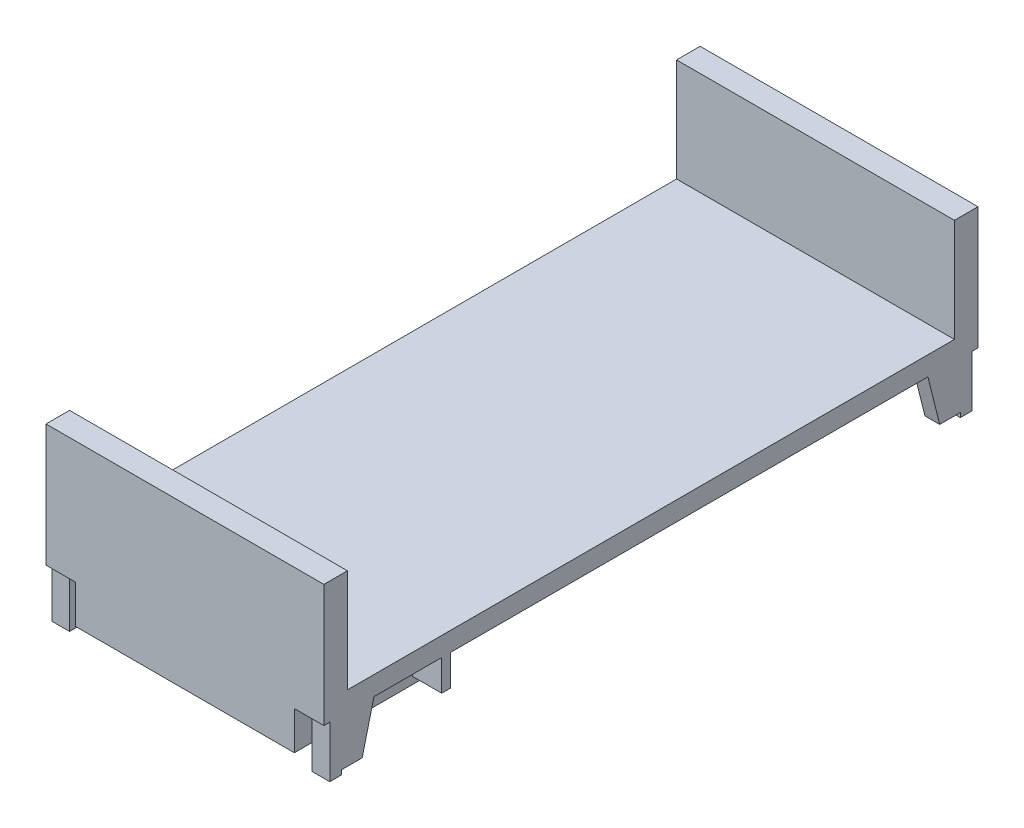
SolidWorks part; units mm, degrees
note: The reader was unsure of these and kept them because the rebuilt part matched: shared geometry of "Sketch1<3>", "Sketch1<4>", "Sketch9<3>".
ref_plane "Front Plane" through (0, 0, 0) normal (0, 0, 1) x (1, 0, 0)
ref_plane "Top Plane" through (0, 0, 0) normal (0, 1, 0) x (1, 0, 0)
ref_plane "Right Plane" through (0, 0, 0) normal (1, 0, 0) x (0, 0, -1)
sketch "Sketch1" plane through (0, 0, 0) normal (0, 1, 0) x (1, 0, 0)
  line L0 (-411.5, 40) -> (-451.5, 40)
  line L1 (451.5, 0) -> (-451.5, 0)
  line L2 (451.5, 0) -> (451.5, 2180)
  line L3 (451.5, 2180) -> (-451.5, 2180)
  line L4 (-451.5, 0) -> (-451.5, 2180)
  line L5 (-451.5, 0) -> (451.5, 0)
  line L6 (-451.5, 0) -> (-451.5, 50)
  line L7 (-451.5, 50) -> (451.5, 50)
  line L8 (451.5, 0) -> (451.5, 50)
  line L9 (-451.5, 2180) -> (451.5, 2180)
  line L10 (-451.5, 2180) -> (-451.5, 2130)
  line L11 (-451.5, 2130) -> (451.5, 2130)
  line L12 (451.5, 2180) -> (451.5, 2130)
  line L13 (451.5, 0) -> (411.5, 0)
  line L14 (451.5, 0) -> (451.5, 50)
  line L15 (451.5, 50) -> (411.5, 50)
  line L16 (411.5, 0) -> (411.5, 50)
  line L17 (-451.5, 0) -> (-411.5, 0)
  line L18 (-451.5, 0) -> (-451.5, 50)
  line L19 (-451.5, 50) -> (-411.5, 50)
  line L20 (-411.5, 0) -> (-411.5, 50)
  line L21 (-451.5, 2130) -> (-411.5, 2130)
  line L22 (-451.5, 2130) -> (-451.5, 2180)
  line L23 (-451.5, 2180) -> (-411.5, 2180)
  line L24 (-411.5, 2130) -> (-411.5, 2180)
  line L25 (451.5, 2180) -> (411.5, 2180)
  line L26 (451.5, 2180) -> (451.5, 2130)
  line L27 (451.5, 2130) -> (411.5, 2130)
  line L28 (411.5, 2180) -> (411.5, 2130)
  line L29 (451.5, 40) -> (411.5, 40)
  line L30 (-451.5, 2140) -> (-411.5, 2140)
  line L31 (411.5, 2140) -> (451.5, 2140)
  line L33 (-471.5, 2200) -> (471.5, 2200)
  line L34 (-471.5, 2200) -> (-471.5, 2120)
  line L35 (-471.5, 2120) -> (471.5, 2120)
  line L36 (471.5, 2200) -> (471.5, 2120)
  line L37 (-471.5, 60) -> (471.5, 60)
  line L38 (-471.5, 60) -> (-471.5, -20)
  line L39 (-471.5, -20) -> (471.5, -20)
  line L40 (471.5, 60) -> (471.5, -20)
  dimension "D1" = 2180
  dimension "D2" = 903
  dimension "D3" = 50
  dimension "D4" = 50
  dimension "D5" = 40
  dimension "D6" = 40
  dimension "D7" = 40
  dimension "D8" = 40
  dimension "D9" = 40
  dimension "D10" = 40
  dimension "D11" = 40
  dimension "D12" = 20
  dimension "D13" = 10
  dimension "D14" = 20
  dimension "D15" = 20
  dimension "D16" = 10
  dimension "D17" = 20
  dimension "D18" = 20
  dimension "D19" = 20
extrude "Boss-Extrude1" add sketch "Sketch1" against normal blind 65 contours L4 L37 L2 L35
extrude "Boss-Extrude2" add sketch "Sketch1<3>" against normal blind 50 and the other way blind 350 contours L38 L39 L40 L37 | L33 L36 L35 L34
sketch "Sketch1<3>" plane through (0, 0, 0) normal (0, 1, 0) x (1, 0, 0) same geometry as "Sketch1"
extrude "Boss-Extrude3" add sketch "Sketch1<4>" against normal blind 240 contours L28 L31 L26 L3 | L22 L30 L24 L9 | L1 L20 L0 L4 | L2 L29 L16 L1
sketch "Sketch1<4>" plane through (0, 0, 0) normal (0, 1, 0) x (1, 0, 0) same geometry as "Sketch1"
sketch "Sketch3" plane through (451.5, 0, 0) normal (1, 0, 0) x (0, 0, -1)
  line L0 (60, -65) -> (2120, -65) construction
  line L3 (40, -225) -> (110, -225)
  line L4 (2140, -240) -> (2140, -65) construction
  line L5 (2030, -65) -> (2070, -225)
  line L6 (2070, -225) -> (2140, -225)
  line L7 (110, -225) -> (150, -65)
  line L8 (2140, -240) -> (2140, -65) construction
  line L9 (40, -240) -> (40, -65) construction
  line L10 (40, -225) -> (40, -65)
  line L11 (40, -65) -> (150, -65)
  line L12 (2140, -225) -> (2140, -65)
  line L13 (2140, -65) -> (2030, -65)
  dimension "D1" = 160
  dimension "D2" = 110
  dimension "D3" = 160
  dimension "D4" = 110
  dimension "D5" = 70
  dimension "D6" = 70
extrude "Boss-Extrude4" add sketch "Sketch3" against normal blind 30
sketch "Sketch4" plane through (-451.5, 0, -45.75) normal (1, 0, 0) x (0, 0, -1)
  line L0 (2094.25, -225) -> (2094.25, -65)
  line L2 (2094.25, -240) -> (2094.25, -65) construction
  line L3 (104.25, -65) -> (64.25, -225)
  line L5 (1984.25, -65) -> (2024.25, -225)
  line L6 (2024.25, -225) -> (2094.25, -225)
  line L7 (64.25, -225) -> (-5.75, -225)
  line L8 (2094.25, -65) -> (1984.25, -65)
  line L9 (-5.75, -225) -> (-5.75, -65)
  line L10 (-5.75, -65) -> (104.25, -65)
  line L11 (14.25, -65) -> (2074.25, -65) construction
  line L12 (-5.75, -240) -> (-5.75, -65) construction
  dimension "D1" = 110
  dimension "D2" = 160
  dimension "D3" = 110
  dimension "D4" = 160
  dimension "D5" = 70
  dimension "D6" = 70
extrude "Boss-Extrude5" add sketch "Sketch4" along normal blind 30
sketch "Sketch5" plane through (0, -240, 0) normal (0, -1, 0) x (1, 0, 0)
  line L0 (-431.5, -2180) -> (-431.5, 0)
  line L1 (-416.5, -2175) -> (-446.5, -2175)
  line L2 (-416.5, -2175) -> (-416.5, -2145)
  line L3 (-416.5, -2145) -> (-446.5, -2145)
  line L4 (-446.5, -2175) -> (-446.5, -2145)
  line L5 (416.5, -2175) -> (446.5, -2175)
  line L6 (416.5, -2175) -> (416.5, -2145)
  line L7 (416.5, -2145) -> (446.5, -2145)
  line L8 (446.5, -2175) -> (446.5, -2145)
  line L9 (416.5, -35) -> (446.5, -35)
  line L10 (416.5, -35) -> (416.5, -5)
  line L11 (416.5, -5) -> (446.5, -5)
  line L12 (446.5, -35) -> (446.5, -5)
  line L13 (-446.5, -35) -> (-416.5, -35)
  line L14 (-446.5, -35) -> (-446.5, -5)
  line L15 (-446.5, -5) -> (-416.5, -5)
  line L16 (-416.5, -35) -> (-416.5, -5)
  line L17 (-451.5, -2160) -> (451.5, -2160)
  line L18 (-411.5, 0) -> (-451.5, 0) construction
  line L19 (-451.5, 0) -> (-451.5, -40) construction
  line L20 (451.5, 0) -> (411.5, 0) construction
  line L21 (451.5, 0) -> (451.5, -40) construction
  line L22 (-451.5, -20) -> (451.5, -20)
  line L25 (431.5, 0) -> (431.5, -2180)
  line L27 (451.5, -2180) -> (411.5, -2180) construction
  line L32 (451.5, -2140) -> (451.5, -2180) construction
  line L33 (-451.5, -2140) -> (-451.5, -2180) construction
  line L34 (-411.5, -2180) -> (-451.5, -2180) construction
  point P16 (-446.5, -2160)
  point P29 (-431.5, -5)
  point P36 (-446.5, -20)
  point P43 (431.5, -2175)
  dimension "D1" = 30
extrude "Cut-Extrude1" cut sketch "Sketch5" against normal blind 200 contours L4 L3 L2 L1 | L6 L7 L8 L5 | L10 L11 L12 L9 | L14 L15 L16 L13
sketch "Sketch6" plane through (0, 0, 20) normal (0, 0, 1) x (1, 0, 0)
  line L1 (130, -65) -> (-130, -65)
  line L2 (-471.5, -65) -> (471.5, -65) construction
  arc A0 (-130, -65) -> (130, -65) centre (0, -65) ccw
  dimension "D1" = 130
extrude "Boss-Extrude6" add sketch "Sketch6" against normal blind 30
sketch "Sketch7" plane through (0, 0, -2200) normal (0, 0, -1) x (-1, 0, 0)
  line L1 (130, -65) -> (-130, -65)
  line L2 (471.5, -65) -> (-471.5, -65) construction
  arc A0 (130, -65) -> (-130, -65) centre (0, -65) cw
  dimension "D1" = 130
extrude "Boss-Extrude7" add sketch "Sketch7" against normal blind 30
sketch3d "3DSketch1"
  line L0 (0, -195, -10) -> (0, -155, -10)
  line L1 (0, -155, -10) -> (0, -155, -2170)
  line L2 (0, -155, -2170) -> (0, -195, -2170)
  line L3 (0, -195, -2170) -> (0, -195, -10)
  arc A0 (-130, -65, -10) -> (130, -65, -10) centre (0, -65, -10) ccw construction
  arc A1 (130, -65, -2170) -> (-130, -65, -2170) centre (0, -65, -2170) ccw construction
  point P6 (0, -65, 120)
  point P12 (0, -65, -2300)
  dimension "D1" = 40
extrude "Boss-Extrude8" add sketch "3DSketch1" along a picked direction on the side of the normal blind 20 and the other way blind 20 contours L1 L2 L3 L0
sketch "Sketch8" plane through (0, -65, 0) normal (0, -1, 0) x (1, 0, 0)
  line L0 (130, 20) -> (471.5, 20) construction
  line L1 (-371.5, 20) -> (371.5, 20)
  line L2 (-371.5, 20) -> (-371.5, -430)
  line L3 (-371.5, -430) -> (371.5, -430)
  line L4 (371.5, 20) -> (371.5, -430)
  line L5 (451.5, -150) -> (451.5, -2030) construction
  line L6 (-371.5, -205) -> (-451.5, -205)
  line L7 (-451.5, -150) -> (-451.5, -2030) construction
  line L8 (371.5, -205) -> (451.5, -205)
  dimension "D1" = 80
  dimension "D2" = 450
extrude "Boss-Extrude9" add sketch "Sketch8" along normal blind 130 contours L1 L4 L3 L2
sketch "Sketch9" plane through (0, 0, -430) normal (0, 0, -1) x (-1, 0, 0)
  line L0 (-371.5, -195) -> (-371.5, -65) construction
  line L1 (-371.5, -100) -> (-321.5, -100)
  line L2 (-371.5, -100) -> (-371.5, -50)
  line L3 (-371.5, -50) -> (-321.5, -50)
  line L4 (-321.5, -100) -> (-321.5, -50)
  line L5 (371.5, -150) -> (321.5, -150)
  line L6 (371.5, -150) -> (371.5, -100)
  line L7 (371.5, -100) -> (321.5, -100)
  line L8 (321.5, -150) -> (321.5, -100)
  line L9 (371.5, -195) -> (371.5, -65) construction
  line L10 (371.5, -65) -> (-371.5, -65) construction
  line M14 (371.5, -195) -> (371.5, -65)
  line M16 (-371.5, -65) -> (-371.5, -195)
  dimension "D1" = 50
  dimension "D2" = 50
  dimension "D3" = 35
  dimension "D4" = 85
extrude "Boss-Extrude11" add sketch "Sketch9" along normal blind 750 contours L1 L4 L3 M16
extrude "Boss-Extrude12" add sketch "Sketch9<3>" along normal offset from surface (1170 mm away) 600 contours L8 L5 L7 M14 up to face at (0, 51.6667, -2200)
sketch "Sketch9<3>" plane through (0, 0, -430) normal (0, 0, -1) x (-1, 0, 0) same geometry as "Sketch9"
sketch "Sketch10" plane through (0, -150, 0) normal (0, -1, 0) x (1, 0, 0)
  line L0 (-371.5, -1600) -> (-371.5, -430) construction
  line L1 (-321.5, -1600) -> (-371.5, -1600)
  line L2 (-321.5, -1600) -> (-321.5, -1550)
  line L3 (-321.5, -1550) -> (-371.5, -1550)
  line L4 (-371.5, -1600) -> (-371.5, -1550)
extrude "Boss-Extrude13" add sketch "Sketch10" against normal up to surface (85 mm away) up to face at (13.1087, -65, -1068.6957)
sketch "Sketch12" plane through (-451.5, 0, 0) normal (-1, 0, 0) x (0, 0, 1)
  line L16 (-60, 0) -> (-2120, 0)
  line L17 (-2120, 0) -> (-2120, -65)
  line L18 (-2120, -65) -> (-2180, -65)
  line L19 (-2180, -65) -> (-2180, -240)
  line L20 (-2180, -240) -> (-2140, -240)
  line L21 (-2140, -240) -> (-2140, -225)
  line L22 (-2140, -225) -> (-2070, -225)
  line L23 (-2070, -225) -> (-2030, -65)
  line L24 (-2030, -65) -> (-150, -65)
  line L25 (-150, -65) -> (-110, -225)
  line L26 (-110, -225) -> (-40, -225)
  line L27 (-40, -225) -> (-40, -240)
  line L28 (-40, -240) -> (0, -240)
  line L29 (0, -240) -> (0, -65)
  line L30 (0, -65) -> (-60, -65)
  line L31 (-60, -65) -> (-60, 0)
  line L32 (-60, 0) -> (-2120, 0)
  line L33 (-2120, 0) -> (-2120, -65)
  line L34 (-2120, -65) -> (-2180, -65)
  line L35 (-2180, -65) -> (-2180, -240)
  line L36 (-2180, -240) -> (-2140, -240)
  line L37 (-2140, -240) -> (-2140, -225)
  line L38 (-2140, -225) -> (-2070, -225)
  line L39 (-2070, -225) -> (-2030, -65)
  line L40 (-2030, -65) -> (-150, -65)
  line L41 (-150, -65) -> (-110, -225)
  line L42 (-110, -225) -> (-40, -225)
  line L43 (-40, -225) -> (-40, -240)
  line L44 (-40, -240) -> (0, -240)
  line L45 (0, -240) -> (0, -65)
  line L46 (0, -65) -> (-60, -65)
  line L47 (-60, -65) -> (-60, 0)
  dimension "D1" = 0
extrude "Boss-Extrude14" add sketch "Sketch12" along normal blind 20
sketch "Sketch13" plane through (451.5, 0, 0) normal (1, 0, 0) x (0, 0, -1)
  line L16 (2120, 0) -> (60, 0)
  line L17 (60, 0) -> (60, -65)
  line L18 (60, -65) -> (0, -65)
  line L19 (0, -65) -> (0, -240)
  line L20 (0, -240) -> (40, -240)
  line L21 (40, -240) -> (40, -225)
  line L22 (40, -225) -> (110, -225)
  line L23 (110, -225) -> (150, -65)
  line L24 (150, -65) -> (2030, -65)
  line L25 (2030, -65) -> (2070, -225)
  line L26 (2070, -225) -> (2140, -225)
  line L27 (2140, -225) -> (2140, -240)
  line L28 (2140, -240) -> (2180, -240)
  line L29 (2180, -240) -> (2180, -65)
  line L30 (2180, -65) -> (2120, -65)
  line L31 (2120, -65) -> (2120, 0)
  line L32 (2120, 0) -> (60, 0)
  line L33 (60, 0) -> (60, -65)
  line L34 (60, -65) -> (0, -65)
  line L35 (0, -65) -> (0, -240)
  line L36 (0, -240) -> (40, -240)
  line L37 (40, -240) -> (40, -225)
  line L38 (40, -225) -> (110, -225)
  line L39 (110, -225) -> (150, -65)
  line L40 (150, -65) -> (2030, -65)
  line L41 (2030, -65) -> (2070, -225)
  line L42 (2070, -225) -> (2140, -225)
  line L43 (2140, -225) -> (2140, -240)
  line L44 (2140, -240) -> (2180, -240)
  line L45 (2180, -240) -> (2180, -65)
  line L46 (2180, -65) -> (2120, -65)
  line L47 (2120, -65) -> (2120, 0)
  dimension "D1" = 0
extrude "Boss-Extrude15" add sketch "Sketch13" along normal blind 20
sketch3d "3DSketch2"
  line L0 (471.5, 0, -2200) -> (-471.5, 0, -2200)
  line L1 (471.5, -65, -2200) -> (471.5, 350, -2200) construction
  line L2 (-471.5, -65, -2200) -> (-471.5, 350, -2200) construction
  line L3 (0, 350, -2200) -> (0, 0, -2200)
  line L4 (-471.5, 350, -2200) -> (471.5, 350, -2200) construction
sketch "Sketch14" plane through (0, -65, 0) normal (0, -1, 0) x (1, 0, 0)
  line L0 (-471.5, -2030) -> (-471.5, -150) construction
  line L1 (-471.5, -380) -> (471.5, -380)
  line L2 (-471.5, -380) -> (-471.5, -410)
  line L3 (-471.5, -410) -> (471.5, -410)
  line L4 (471.5, -380) -> (471.5, -410)
  line L5 (471.5, -150) -> (471.5, -2030) construction
  line L6 (-411.5, 0) -> (-471.5, 0) construction
  dimension "D1" = 380
  dimension "D2" = 30
extrude "Boss-Extrude16" add sketch "Sketch14" along normal offset from surface (105 mm away) 170 up to face at (235.75, 0, -1090)
